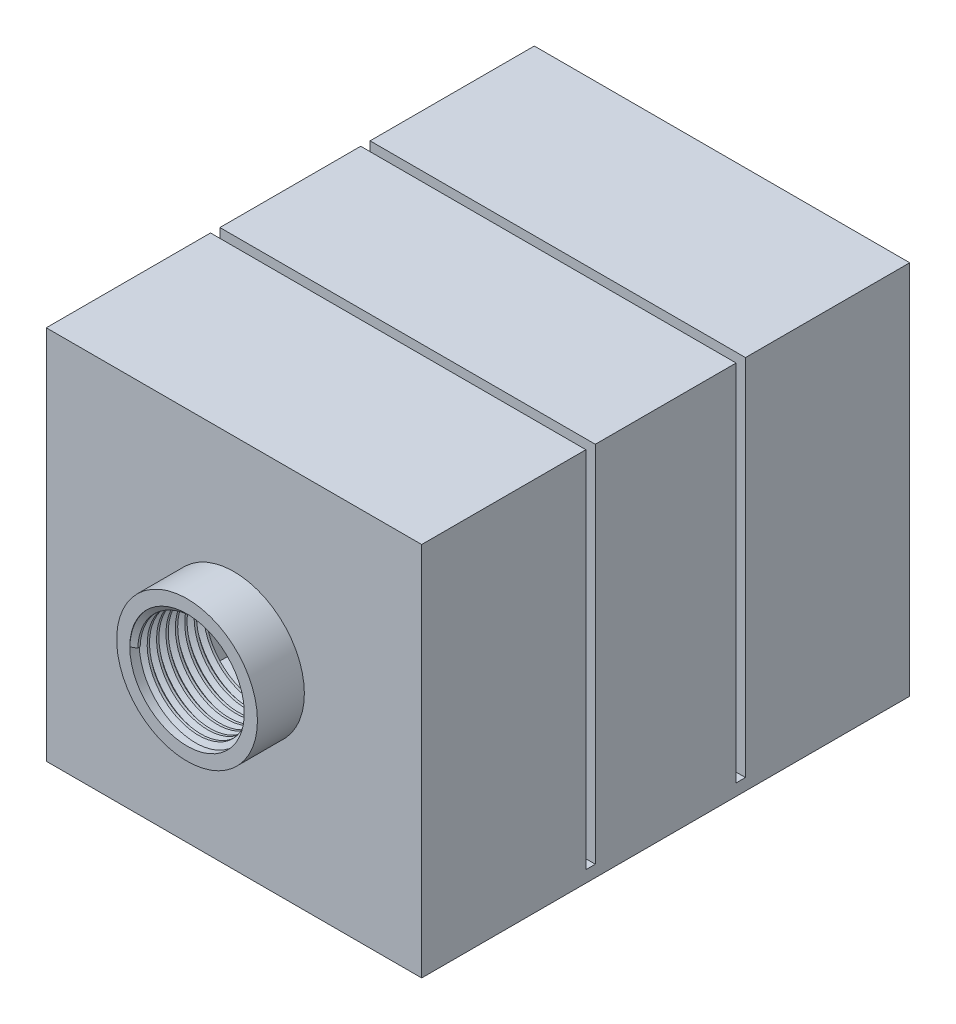
SolidWorks part; units mm, degrees
ref_plane "Front Plane" through (0, 0, 0) normal (0, 0, 1) x (1, 0, 0)
ref_plane "Top Plane" through (0, 0, 0) normal (0, 1, 0) x (1, 0, 0)
ref_plane "Right Plane" through (0, 0, 0) normal (1, 0, 0) x (0, 0, -1)
sketch "Sketch1" plane through (0, 0, 0) normal (0, 0, 1) x (1, 0, 0)
  line L1 (-40, -40) -> (40, -40)
  line L2 (-40, -40) -> (-40, 40)
  line L3 (-40, 40) -> (40, 40)
  line L4 (40, -40) -> (40, 40)
  line L5 (-40, -40) -> (40, 40) construction
  line L6 (-40, 40) -> (40, -40) construction
  line L7 (-35, -35) -> (35, -35)
  line L8 (-35, -35) -> (-35, 35)
  line L9 (-35, 35) -> (35, 35)
  line L10 (35, -35) -> (35, 35)
  line L11 (-35, -35) -> (35, 35) construction
  line L12 (-35, 35) -> (35, -35) construction
  point P0 (0, 0)
  point P6 (0, 0)
extrude "Boss-Extrude1" add sketch "Sketch1" along normal blind 30
sketch "Sketch2" plane through (0, 0, 0) normal (0, 0, -1) x (-1, 0, 0)
  line L0 (40, 40) -> (40, -40) construction
  line L1 (-40, -40) -> (40, -40)
  line L2 (-40, -40) -> (-40, -37.5)
  line L3 (-40, -37.5) -> (40, -37.5)
  line L4 (40, -40) -> (40, -37.5)
extrude "Boss-Extrude2" add sketch "Sketch2" along normal blind 2
sketch "Sketch3" plane through (0, 0, -2) normal (0, 0, -1) x (-1, 0, 0)
  line L1 (-35, -35) -> (35, -35)
  line L2 (-35, -35) -> (-35, 35)
  line L3 (-35, 35) -> (35, 35)
  line L4 (35, -35) -> (35, 35)
  line L5 (-40, 40) -> (40, 40)
  line L6 (-40, 40) -> (-40, -40)
  line L7 (-40, -40) -> (40, -40)
  line L8 (40, 40) -> (40, -40)
extrude "Boss-Extrude3" add sketch "Sketch3" along normal blind 30
sketch "Sketch4" plane through (0, 0, -32) normal (0, 0, -1) x (-1, 0, 0)
  line L0 (40, -40) -> (40, 40) construction
  line L1 (-40, -40) -> (40, -40)
  line L2 (-40, -40) -> (-40, -37.5)
  line L3 (-40, -37.5) -> (40, -37.5)
  line L4 (40, -40) -> (40, -37.5)
extrude "Boss-Extrude4" add sketch "Sketch4" along normal blind 2
sketch "Sketch5" plane through (0, 0, -34) normal (0, 0, -1) x (-1, 0, 0)
  line L1 (-40, -40) -> (40, -40)
  line L2 (-40, -40) -> (-40, 40)
  line L3 (-40, 40) -> (40, 40)
  line L4 (40, -40) -> (40, 40)
  line L5 (-35, -35) -> (35, -35)
  line L6 (-35, -35) -> (-35, 35)
  line L7 (-35, 35) -> (35, 35)
  line L8 (35, -35) -> (35, 35)
extrude "Boss-Extrude5" add sketch "Sketch5" along normal blind 30
sketch "Sketch6" plane through (0, 0, -64) normal (0, 0, -1) x (-1, 0, 0)
  line L1 (-40, 40) -> (40, 40)
  line L2 (-40, 40) -> (-40, -40)
  line L3 (-40, -40) -> (40, -40)
  line L4 (40, 40) -> (40, -40)
  circle A0 centre (0, 0) radius 12.2
extrude "Boss-Extrude6" add sketch "Sketch6" along normal blind 15
sketch "Sketch7" plane through (0, 0, -79) normal (0, 0, -1) x (-1, 0, 0)
  line L1 (-40, 40) -> (40, 40)
  line L2 (-40, 40) -> (-40, -40)
  line L3 (-40, -40) -> (40, -40)
  line L4 (40, 40) -> (40, -40)
  circle A0 centre (0, 0) radius 16
extrude "Cut-Extrude1" cut sketch "Sketch7" against normal blind 10
thread "Thread1" pitch 2 method extrude profile "Thread Profile1" start angle 0, offset 0, length 14, pitch 2, diameter 24.4
ref_plane "Plane4" through (12.2, 0, -79) normal (0, -1, 0) x (1, 0, 0)
sketch "Thread Profile1" plane through (12.2, 0, -79) normal (0, -1, 0) x (1, 0, 0)
  line L0 (0, 0) -> (0, 2) construction
  line L11 (0, 0) -> (0, 1.75)
  line L12 (0, 1.75) -> (-1.0825, 1.125)
  line L13 (-1.0825, 1.125) -> (-1.0825, 0.625)
  line L15 (-1.0825, 0.625) -> (0, 0)
  line L17 (-1.0825, 0.875) -> (0, 0.875) construction
  point P2 (0, 0)
  dimension "Pitch" = 2
  dimension "Profile_Angle" = 60
  dimension "Profile_Land" = 0.5
  dimension "Profile_Height" = 1.0825
sketch "Sketch10" plane through (0, 0, 30) normal (0, 0, 1) x (1, 0, 0)
  line L1 (-40, 40) -> (40, 40)
  line L2 (-40, 40) -> (-40, -40)
  line L3 (-40, -40) -> (40, -40)
  line L4 (40, 40) -> (40, -40)
  circle A0 centre (0, 0) radius 12.2
extrude "Boss-Extrude7" add sketch "Sketch10" along normal blind 15
sketch "Sketch11" plane through (0, 0, 45) normal (0, 0, 1) x (1, 0, 0)
  line L1 (-40, 40) -> (40, 40)
  line L2 (-40, 40) -> (-40, -40)
  line L3 (-40, -40) -> (40, -40)
  line L4 (40, 40) -> (40, -40)
  circle A0 centre (0, 0) radius 15
extrude "Cut-Extrude2" cut sketch "Sketch11" against normal blind 10
thread "Thread2" pitch 2 method extrude profile "Thread Profile2" start angle 0, offset 0, length 14, pitch 2, diameter 24.4
ref_plane "Plane5" through (-12.2, 0, 45) normal (0, -1, 0) x (-1, 0, 0)
sketch "Thread Profile2" plane through (-12.2, 0, 45) normal (0, -1, 0) x (-1, 0, 0)
  line L0 (0, 0) -> (0, 2) construction
  line L11 (0, 0) -> (0, 1.75)
  line L12 (0, 1.75) -> (-1.0825, 1.125)
  line L13 (-1.0825, 1.125) -> (-1.0825, 0.625)
  line L15 (-1.0825, 0.625) -> (0, 0)
  line L17 (-1.0825, 0.875) -> (0, 0.875) construction
  point P2 (0, 0)
  dimension "Pitch" = 2
  dimension "Profile_Angle" = 60
  dimension "Profile_Land" = 0.5
  dimension "Profile_Height" = 1.0825
